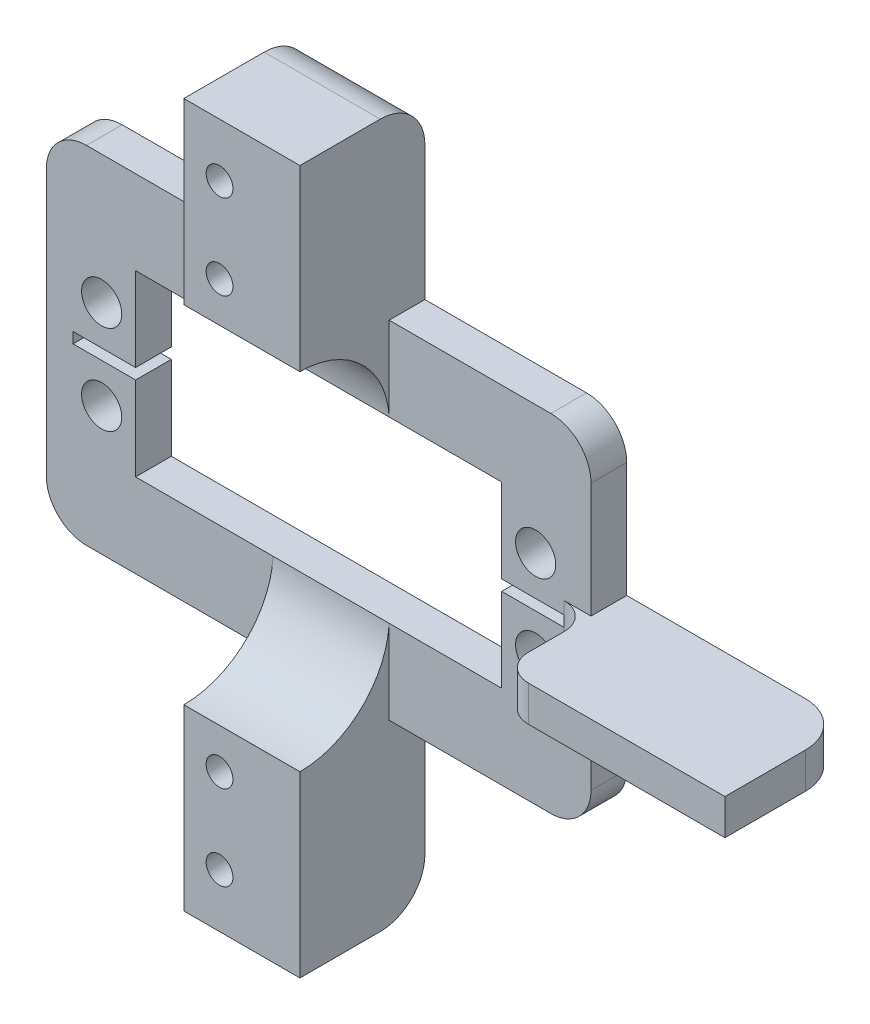
SolidWorks part; units mm, degrees
ref_plane "Plano frontal" through (0, 0, 0) normal (0, 0, 1) x (1, 0, 0)
ref_plane "Plano superior" through (0, 0, 0) normal (0, 1, 0) x (1, 0, 0)
ref_plane "Plano direito" through (0, 0, 0) normal (1, 0, 0) x (0, 0, -1)
sketch "Esboço1" plane through (0, 0, 0) normal (0, 0, 1) x (1, 0, 0)
  line L0 (-0.5, 40.45) -> (-0.5, 20.45) construction
  line L1 (30, 30.45) -> (30, 15.55)
  line L2 (30, 30.45) -> (30, 45.35)
  line L3 (24.5, 49.85) -> (25.5, 49.85)
  line L5 (-28, 30.45) -> (-31, 30.45) construction
  line L10 (27, 30.45) -> (27, 31.05)
  line L11 (27, 31.05) -> (20, 31.05)
  line L16 (-31, 30.45) -> (-31, 15.55)
  line L17 (-26.5, 11.05) -> (25.5, 11.05)
  line L21 (20, 31.05) -> (20, 29.85)
  line L22 (20, 29.85) -> (27, 29.85)
  line L23 (27, 29.85) -> (27, 30.45)
  line L24 (20, 30.45) -> (20, 40.45)
  line L25 (20, 40.45) -> (-21, 40.45)
  line L26 (-21, 40.45) -> (-21, 20.45)
  line L27 (-21, 20.45) -> (20, 20.45)
  line L28 (20, 20.45) -> (20, 30.45)
  line L29 (-21, 30.45) -> (-21, 31.05)
  line L30 (-21, 31.05) -> (-28, 31.05)
  line L31 (-28, 31.05) -> (-28, 29.85)
  line L32 (-28, 29.85) -> (-21, 29.85)
  line L36 (-21, 29.85) -> (-21, 30.45)
  line L37 (20, 40.45) -> (23.8, 40.45) construction
  line L38 (23.8, 40.45) -> (23.8, 35.45) construction
  line L39 (23.8, 35.45) -> (23.8, 25.45) construction
  line L40 (-21, 40.45) -> (-24.8, 40.45) construction
  line L41 (-24.8, 40.45) -> (-24.8, 35.45) construction
  line L42 (-24.8, 35.45) -> (-24.8, 25.45) construction
  line L43 (-31, 30.45) -> (-31, 45.35)
  line L45 (-26.5, 49.85) -> (24.5, 49.85)
  line L53 (27, 9.55) -> (27, 9.4834)
  arc A0 (25.5, 11.05) -> (30, 15.55) centre (25.5, 15.55) ccw
  arc A1 (25.5, 49.85) -> (30, 45.35) centre (25.5, 45.35) cw
  arc A2 (-26.5, 49.85) -> (-31, 45.35) centre (-26.5, 45.35) ccw
  arc A3 (-26.5, 11.05) -> (-31, 15.55) centre (-26.5, 15.55) cw
  circle A6 centre (23.8, 35.45) radius 2.25
  circle A7 centre (23.8, 25.45) radius 2.25
  circle A8 centre (-24.8, 35.45) radius 2.25
  circle A9 centre (-24.8, 25.45) radius 2.25
  point P64 (27, 49.85)
  point P80 (27, 11.05)
  dimension "D9" = 4.5
  dimension "D10" = 4.5
extrude "Ressalto-extrusão1" add sketch "Esboço1" along normal blind 4
sketch "Esboço2" plane through (0, 0, 4) normal (0, 0, 1) x (1, 0, 0)
  line L2 (9.5, 30.45) -> (9.5, 49.85) construction
  line L3 (-26.5, 49.85) -> (25.5, 49.85) construction
  line L4 (9.5, 30.45) -> (30, 30.45) construction
  line L5 (30, 45.35) -> (30, 15.55) construction
  line L6 (9.5, 30.45) -> (9.5, 11.05) construction
  line L7 (-26.5, 11.05) -> (25.5, 11.05) construction
  line L8 (9.5, 49.85) -> (7.4, 49.85)
  line L9 (7.4, 49.85) -> (7.4, 69.85)
  line L10 (7.4, 69.85) -> (4.4, 69.85)
  line L11 (4.4, 69.85) -> (4.4, 49.85)
  line L12 (7.4, 69.85) -> (7.4, 63.85) construction
  line L13 (7.4, 63.85) -> (-1.6, 63.85) construction
  line L14 (-1.6, 63.85) -> (-1.6, 54.35) construction
  line L15 (4.4, 69.85) -> (-5.6, 69.85)
  line L16 (-5.6, 69.85) -> (-5.6, 49.85)
  line L17 (-5.6, 49.85) -> (7.4, 49.85)
  line L18 (-1.6, -2.95) -> (-1.6, 6.55) construction
  line L19 (7.4, -2.95) -> (-1.6, -2.95) construction
  line L20 (7.4, -8.95) -> (7.4, -2.95) construction
  line L21 (-5.6, 11.05) -> (7.4, 11.05)
  line L22 (-5.6, -8.95) -> (-5.6, 11.05)
  line L23 (4.4, -8.95) -> (-5.6, -8.95)
  line L24 (4.4, -8.95) -> (4.4, 11.05)
  line L25 (7.4, -8.95) -> (4.4, -8.95)
  line L26 (7.4, 11.05) -> (7.4, -8.95)
  line L27 (30, 30.45) -> (30, 32.45)
  line L28 (30, 32.45) -> (55, 32.45)
  line L29 (55, 32.45) -> (55, 28.45)
  line L30 (55, 28.45) -> (30, 28.45)
  line L31 (30, 28.45) -> (30, 32.45)
  circle A0 centre (9.5, 30.45) radius 5
  circle A1 centre (23.8, 35.45) radius 2.25
  circle A3 centre (-1.6, 63.85) radius 1.5
  circle A4 centre (23.8, 35.45) radius 2.25
  circle A5 centre (23.8, 35.45) radius 2.25
  circle A6 centre (-1.6, 54.35) radius 1.5
  circle A7 centre (-1.6, 6.55) radius 1.5
  circle A8 centre (-1.6, -2.95) radius 1.5
  line M7 (-26.5, 11.05) -> (25.5, 11.05)
  line M9 (30, 15.55) -> (30, 45.35)
  line M11 (25.5, 49.85) -> (-26.5, 49.85)
  dimension "D1" = 0
extrude "Ressalto-extrusão2" add sketch "Esboço2" along normal blind 10 and the other way blind 4 contours L15 L16 L11 A6 A3 M11 | L10 L11 L9 M11 | L30 L29 L28 M9 | L23 L24 L22 A7 A8 M7 | L26 L21 L24 L25
fillet "Filete1" radius 3 1 edges at (30, 30.45, 4)
fillet "Filete2" radius 3 1 edges at (30, 30.45, 14)
fillet "Filete3" radius 10 1 edges at (0.9, 11.05, 4)
fillet "Filete4" radius 10 1 edges at (0.9, 49.85, 4)
fillet "Filete6" radius 5 1 edges at (0.9, 69.85, 0)
fillet "Filete7" radius 5 1 edges at (0.9, -8.95, 0)
fillet "Filete8" radius 5 1 edges at (55, 30.45, 0)
